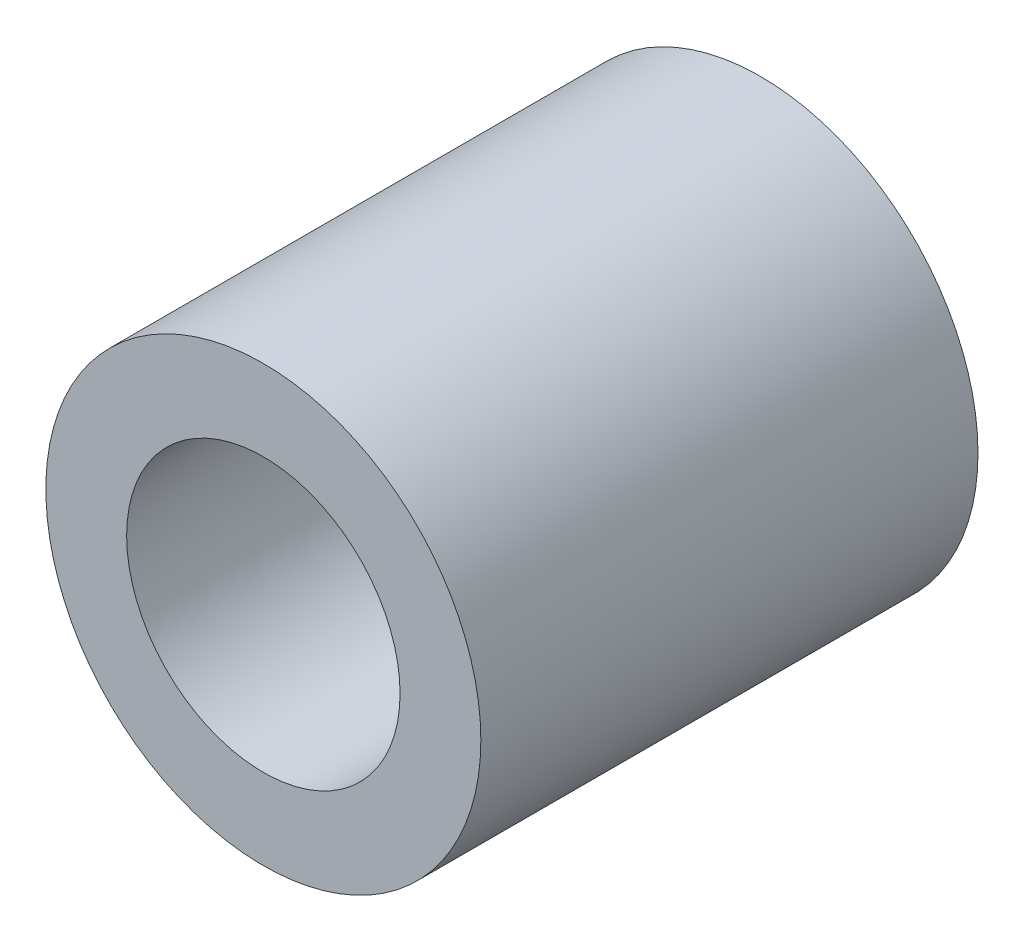
SolidWorks part; units mm, degrees
ref_plane "Front Plane" through (0, 0, 0) normal (0, 0, 1) x (1, 0, 0)
ref_plane "Top Plane" through (0, 0, 0) normal (0, 1, 0) x (1, 0, 0)
ref_plane "Right Plane" through (0, 0, 0) normal (1, 0, 0) x (0, 0, -1)
sketch "Sketch1" plane through (0, 0, 0) normal (0, 0, 1) x (1, 0, 0)
  circle A0 centre (0, 0) radius 4.4
  circle A1 centre (0, 0) radius 7
extrude "Boss-Extrude1" add sketch "Sketch1" along normal blind 16
